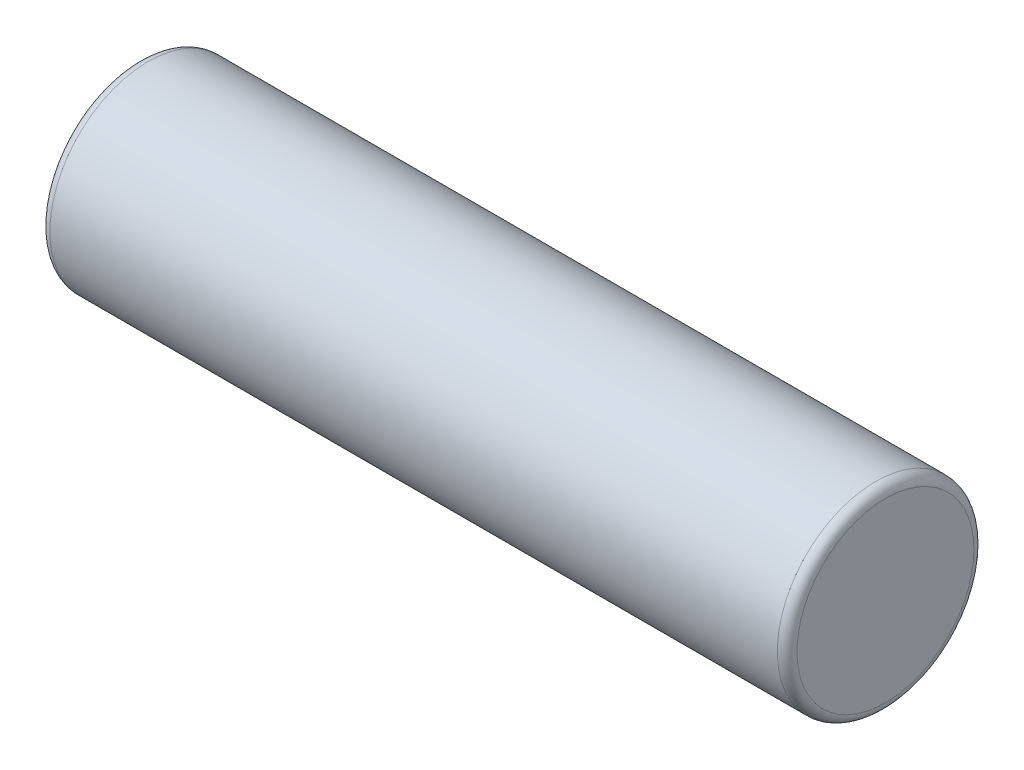
SolidWorks part; units mm, degrees
ref_plane "Front Plane" through (0, 0, 0) normal (0, 0, 1) x (1, 0, 0)
ref_plane "Top Plane" through (0, 0, 0) normal (0, 1, 0) x (1, 0, 0)
ref_plane "Right Plane" through (0, 0, 0) normal (1, 0, 0) x (0, 0, -1)
sketch "Sketch1" plane through (0, 0, 0) normal (1, 0, 0) x (0, 0, -1)
  circle A0 centre (0, 0) radius 10
  dimension "D1" = 20
extrude "Boss-Extrude1" add sketch "Sketch1" along normal blind 38 and the other way blind 38
fillet "Fillet1" radius 1 2 edges at (-38, 0, -10) (38, 0, -10)
